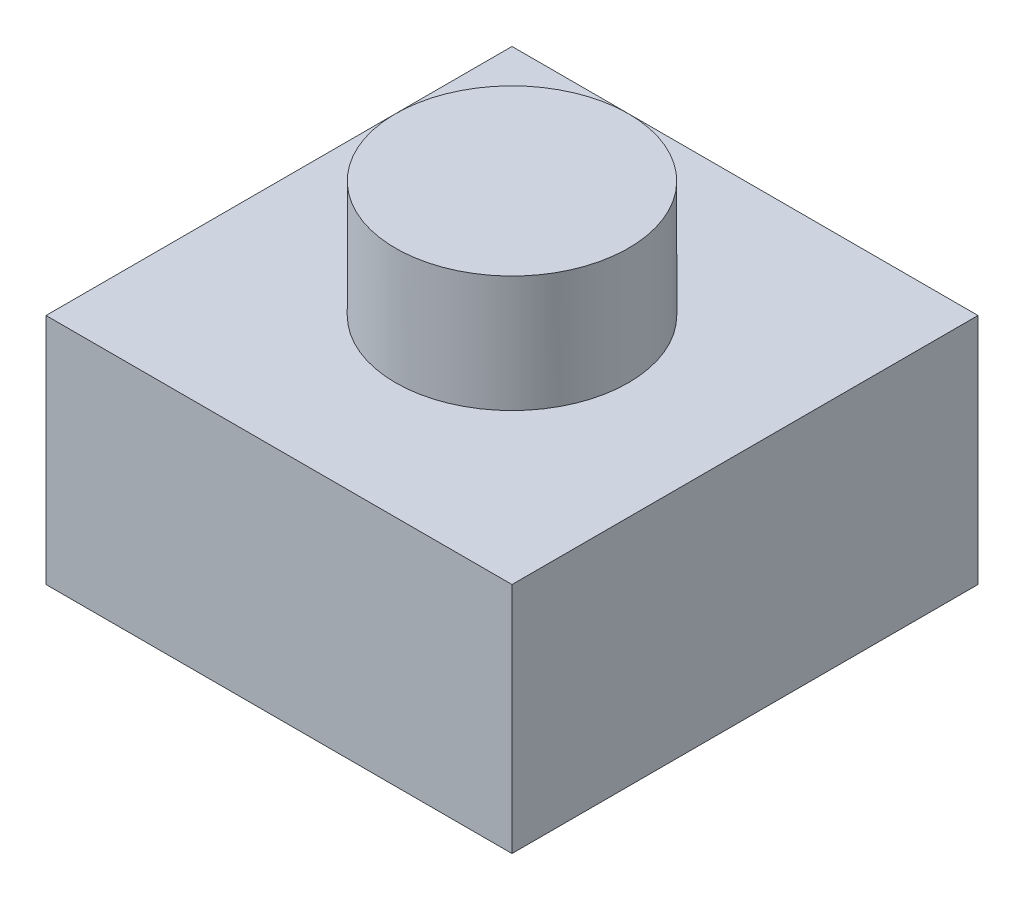
SolidWorks part; units mm, degrees
ref_plane "Front" through (0, 0, 0) normal (0, 0, 1) x (1, 0, 0)
ref_plane "Top" through (0, 0, 0) normal (0, 1, 0) x (1, 0, 0)
ref_plane "Right" through (0, 0, 0) normal (1, 0, 0) x (0, 0, -1)
sketch "Sketch1" plane through (0, 0, 0) normal (0, 1, 0) x (1, 0, 0)
  line L1 (0, 0) -> (80, 0)
  line L2 (0, 0) -> (0, 80)
  line L3 (0, 80) -> (80, 80)
  line L4 (80, 0) -> (80, 80)
  line L5 (40, 80) -> (40, 0) construction
  line L6 (0, 40) -> (80, 40) construction
  circle A0 centre (40, 40) radius 20
  point P360 (40, 40)
  dimension "D3" = 40
  dimension "D1" = 80
  dimension "D2" = 80
extrude "Boss-Extrude1" add sketch "Sketch1" along normal blind 40
extrude "Boss-Extrude2" add sketch "Sketch1<3>" along direction (0, -1, 0) on the side of the normal offset from surface (60 mm away) 20 contours A0 region at (40, 0, -40) up to face at (40, 40, -40) offset beyond the face yes
sketch "Sketch1<3>" plane through (0, 0, 0) normal (0, 1, 0) x (1, 0, 0) same geometry as "Sketch1"
